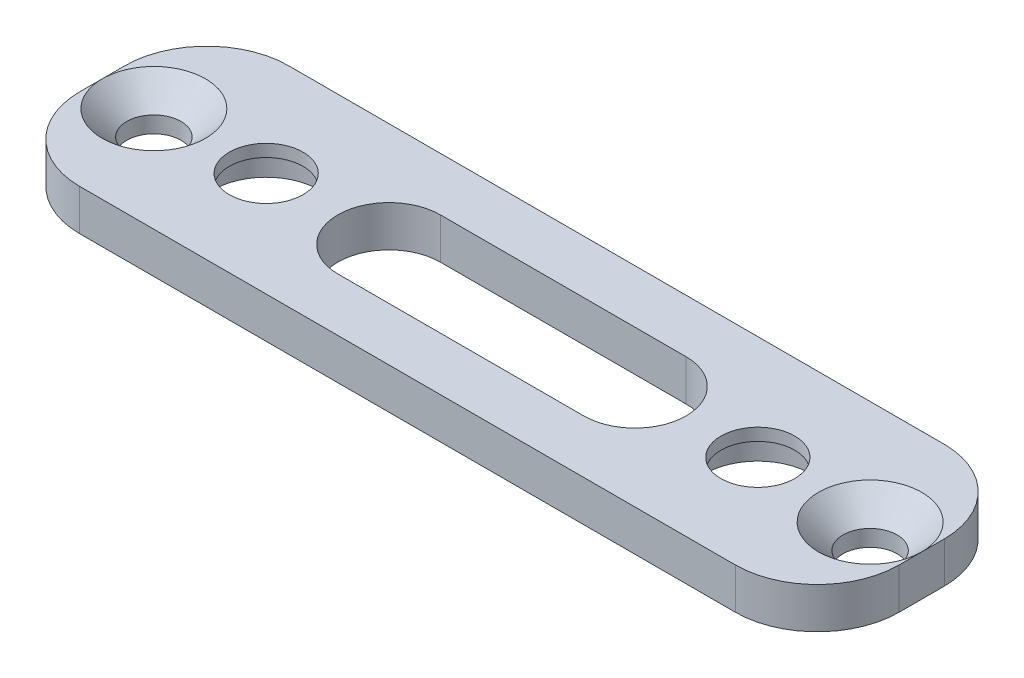
SolidWorks part; units mm, degrees
ref_plane "Front Plane" through (0, 0, 0) normal (0, 0, 1) x (1, 0, 0)
ref_plane "Top Plane" through (0, 0, 0) normal (0, 1, 0) x (1, 0, 0)
ref_plane "Right Plane" through (0, 0, 0) normal (1, 0, 0) x (0, 0, -1)
sketch "Sketch1" plane through (0, 0, 0) normal (0, 0, 1) x (1, 0, 0)
  line L0 (0, 0) -> (100, 0)
  line L1 (100, 0) -> (100, 7)
  line L2 (100, 7) -> (0, 7)
  line L3 (0, 7) -> (0, 0)
  dimension "D1" = 100
  dimension "D2" = 7
extrude "Boss-Extrude1" add sketch "Sketch1" along normal blind 25.5
sketch "Sketch2" plane through (0, 7, 0) normal (0, 1, 0) x (1, 0, 0)
  line L2 (80, -25.5) -> (80, 0)
  line L3 (80, -25.5) -> (80, 0) construction
  line L7 (100, -25.5) -> (100, 0) construction
  line L8 (0, -12.75) -> (100, -12.75) construction
  line L9 (0, -25.5) -> (0, 0) construction
  line L12 (93.7, -25.5) -> (93.7, 0)
  line L13 (93.7, -25.5) -> (93.7, 0) construction
  line L15 (6.3, -25.5) -> (6.3, 0)
  line L16 (6.3, -25.5) -> (6.3, 0) construction
  line L18 (20, -25.5) -> (20, 0)
  line L19 (20, -25.5) -> (20, 0) construction
  circle A0 centre (80, -12.75) radius 4.5
  circle A1 centre (20, -12.75) radius 4.5
  dimension "D1" = 6.3
  dimension "D2" = 6.3
  dimension "D3" = 20
  dimension "D4" = 20
hole_wizard "CSK for M6 Countersunk Flat Head Screw1" positions "Sketch4" profile "Sketch3" countersink size "M6" standard "ISO" end condition through all
sketch "Sketch4" plane through (0, 7, 0) normal (0, 1, 0) x (1, 0, 0)
  point P0 (93.7, -12.75)
  point P2 (6.2984, -12.75)
sketch "Sketch3" plane through (93.7, 7, 12.75) normal (1, 0, 0) x (0, 0, 1)
  line L0 (0, 0) -> (0, 7)
  line L1 (0, 7) -> (3.3, 7)
  line L2 (3.3, 7) -> (3.3, 3)
  line L3 (3.3, 3) -> (6.3, 0)
  line L5 (6.3, 0) -> (0, 0)
  line L6 (-3.3, 3) -> (-6.3, 0) construction
  line L11 (0, -6.35) -> (0, 107.95) construction
  dimension "Thru Hole Dia." = 6.6
  dimension "Thru Hole Depth" = 7
  dimension "Near C'Sink Dia." = 12.6
  dimension "Near C'Sink Angle" = 90
extrude "Cut-Extrude2" cut sketch "Sketch2" against normal blind 3 contours A1
extrude "Cut-Extrude3" cut sketch "Sketch2<4>" against normal blind 3
sketch "Sketch2<4>" plane through (0, 7, 0) normal (0, 1, 0) x (1, 0, 0) same geometry as "Sketch2"
sketch "Sketch6" plane through (0, 4, 0) normal (0, 1, 0) x (1, 0, 0)
  circle A2 centre (20, -12.75) radius 6.5
  circle A3 centre (20, -12.75) radius 6.5
  circle A5 centre (80, -12.75) radius 6.5
  circle A6 centre (80, -12.75) radius 6.5
  dimension "D1" = 2
  dimension "D2" = 2
extrude "Cut-Extrude4" cut sketch "Sketch6" along normal blind 1.5
sketch "Sketch9" plane through (0, 4, 0) normal (0, 1, 0) x (1, 0, 0)
  circle A0 centre (20, -12.75) radius 6.5
  circle A1 centre (80, -12.75) radius 6.5
extrude "Cut-Extrude5" cut sketch "Sketch9" against normal through all
sketch "Sketch10" plane through (0, 0, 0) normal (0, -1, 0) x (1, 0, 0)
  line L1 (0, 0) -> (100, 0)
  line L2 (0, 0) -> (0, 25.5)
  line L3 (0, 25.5) -> (100, 25.5)
  line L4 (100, 0) -> (100, 25.5)
extrude "Cut-Extrude6" cut sketch "Sketch10" against normal blind 2
sketch "Sketch11" plane through (0, 7, 0) normal (0, 1, 0) x (1, 0, 0)
  line L0 (50, 0) -> (50, -25.5) construction
  line L1 (100, 0) -> (0, 0) construction
  line L2 (100, -25.5) -> (0, -25.5) construction
  line L3 (35, -19) -> (65, -19)
  line L6 (35, -6.5) -> (65, -6.5)
  line L7 (35, -19) -> (65, -6.5) construction
  line L8 (65, -19) -> (35, -6.5) construction
  arc A0 (35, -6.5) -> (35, -19) centre (35, -12.75) ccw
  arc A1 (65, -19) -> (65, -6.5) centre (65, -12.75) ccw
  point P7 (50, -12.75)
  dimension "D1" = 30
  dimension "D2" = 12.5
extrude "Cut-Extrude7" cut sketch "Sketch11" against normal through all
fillet "Fillet4" radius 10 4 edges at (100, 4.5, 25.5) (100, 4.5, 0) (0, 4.5, 0) (0, 4.5, 25.5)
